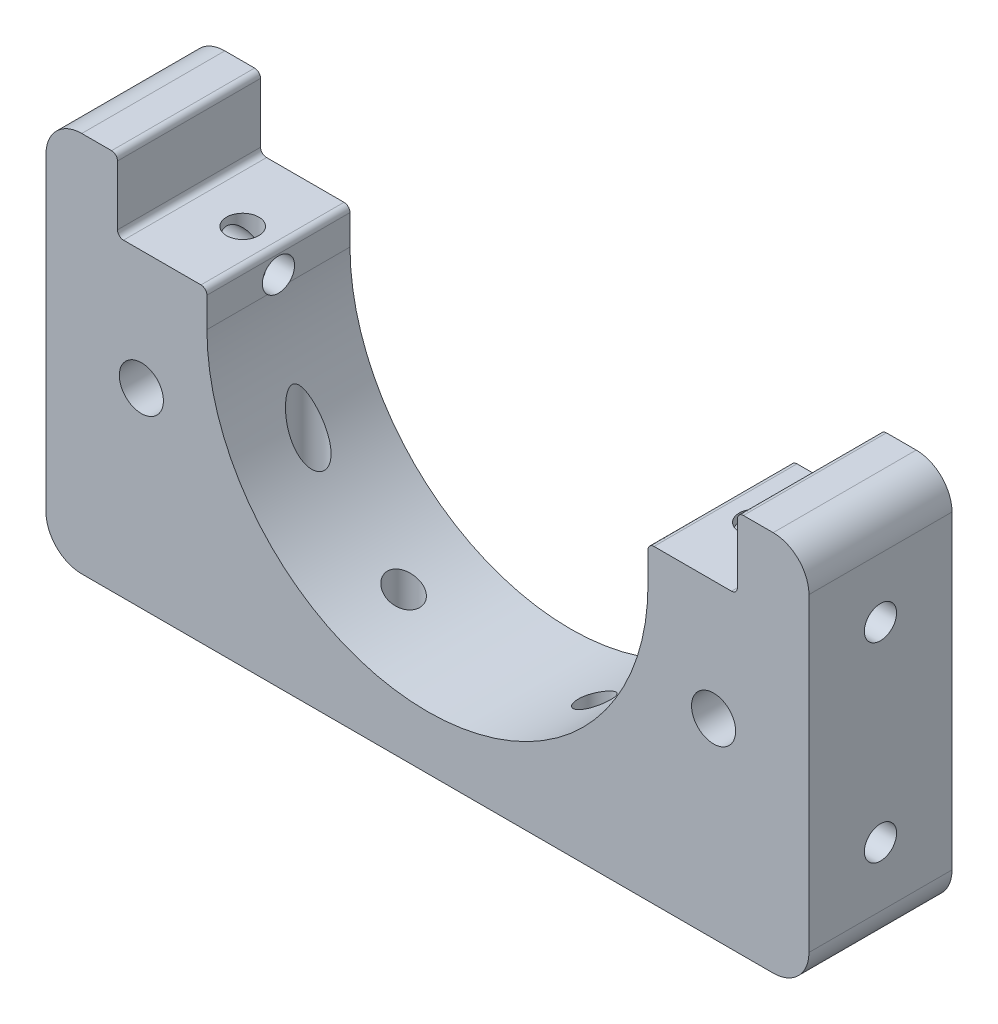
SolidWorks part; units mm, degrees
ref_plane "Front Plane" through (0, 0, 0) normal (0, 0, 1) x (1, 0, 0)
ref_plane "Top Plane" through (0, 0, 0) normal (0, 1, 0) x (1, 0, 0)
ref_plane "Right Plane" through (0, 0, 0) normal (1, 0, 0) x (0, 0, -1)
ref_plane "Plane1" through (0, 0, -6) normal (0, 0, -1) x (-1, 0, 0)
sketch "Sketch1" plane through (0, 0, -6) normal (0, 0, -1) x (-1, 0, 0)
  line L0 (32, -26) -> (32, 6)
  line L1 (32, 6) -> (-32, 6)
  line L2 (-32, 6) -> (-32, -26)
  line L3 (-32, -26) -> (32, -26)
extrude "Boss-Extrude1" add sketch "Sketch1" against normal blind 12
sketch "Sketch2" plane through (0, 0, 6) normal (0, 0, 1) x (1, 0, 0)
  line L0 (-26, 6) -> (-26, 0)
  line L1 (-26, 0) -> (-18.5, 0)
  line L2 (-18.5, 0) -> (-18.5, -3)
  line L3 (18.5, -3) -> (18.5, 6)
  line L4 (18.5, 6) -> (-26, 6)
  arc A0 (-18.5, -3) -> (18.5, -3) centre (0, -3) ccw
extrude "Cut-Extrude1" cut sketch "Sketch2" against normal through all
sketch "Sketch3" plane through (0, 0, 6) normal (0, 0, 1) x (1, 0, 0)
  line L0 (18.5, 0) -> (26, 0)
  line L1 (26, 0) -> (26, 6)
  line L2 (26, 6) -> (18.5, 6)
  line L3 (18.5, 6) -> (18.5, 0)
extrude "Cut-Extrude2" cut sketch "Sketch3" against normal through all
hole_wizard "M2.5 Clearance Hole1" positions "Sketch5" profile "Sketch4" hole size "M2.5" standard "ANSI Metric"
sketch "Sketch5" plane through (0, -26, 0) normal (0, -1, 0) x (-1, 0, 0)
  point P0 (8, 0)
  point P1 (-8, 0)
sketch "Sketch4" plane through (-8, -26, 0) normal (1, 0, 0) x (0, 0, -1)
  line L0 (0, 0) -> (0, 32)
  line L1 (0, 32) -> (1.3525, 32)
  line L2 (1.3525, 32) -> (1.3525, 0)
  line L5 (1.3525, 0) -> (0, 0)
  line L11 (0, -6.35) -> (0, 107.95) construction
  dimension "Thru Hole Dia." = 2.7051
  dimension "Thru Hole Depth" = 32
hole_wizard "M2.5 Clearance Hole2" positions "Sketch7" profile "Sketch6" hole size "M2.5" standard "ANSI Metric"
sketch "Sketch7" plane through (0, -26, 0) normal (0, -1, 0) x (-1, 0, 0)
  point P0 (16, 0)
  point P1 (-16, 0)
sketch "Sketch6" plane through (-16, -26, 0) normal (1, 0, 0) x (0, 0, -1)
  line L0 (0, 0) -> (0, 32)
  line L1 (0, 32) -> (1.3525, 32)
  line L2 (1.3525, 32) -> (1.3525, 0)
  line L5 (1.3525, 0) -> (0, 0)
  line L11 (0, -6.35) -> (0, 107.95) construction
  dimension "Thru Hole Dia." = 2.7051
  dimension "Thru Hole Depth" = 32
hole_wizard "Ø3.7 (3.7) Diameter Hole1" positions "Sketch9" profile "Sketch8" hole size "Ø3.7" standard "ANSI Metric"
sketch "Sketch9" plane through (0, 0, -6) normal (0, 0, -1) x (-1, 0, 0)
  point P0 (24, -10)
sketch "Sketch8" plane through (-24, -10, -6) normal (1, 0, 0) x (0, 1, 0)
  line L0 (0, 0) -> (0, 12)
  line L1 (0, 12) -> (1.85, 12)
  line L2 (1.85, 12) -> (1.85, 0)
  line L5 (1.85, 0) -> (0, 0)
  line L11 (0, -6.35) -> (0, 107.95) construction
  dimension "Thru Hole Dia." = 3.7
  dimension "Thru Hole Depth" = 12
hole_wizard "M2.5 Clearance Hole3" positions "Sketch11" profile "Sketch10" hole size "M2.5" standard "ANSI Metric"
sketch "Sketch11" plane through (0, 0, 0) normal (0, 1, 0) x (1, 0, 0)
  point P0 (21.5, 0)
  point P1 (-21.5, 0)
sketch "Sketch10" plane through (21.5, 0, 0) normal (1, 0, 0) x (0, 0, 1)
  line L0 (0, 0) -> (0, 12.5602)
  line L1 (0, 12.5602) -> (1.3525, 12)
  line L2 (1.3525, 12) -> (1.3525, 0)
  line L5 (1.3525, 0) -> (0, 0)
  line L10 (0, 12.5602) -> (-1.3525, 12) construction
  line L11 (0, -6.35) -> (0, 107.95) construction
  dimension "Hole Dia." = 2.7051
  dimension "Hole Depth" = 12
  dimension "Drill Angle" = 135
hole_wizard "Ø3.7 (3.7) Diameter Hole2" positions "Sketch13" profile "Sketch12" hole size "Ø3.7" standard "ANSI Metric"
sketch "Sketch13" plane through (0, 0, 6) normal (0, 0, 1) x (1, 0, 0)
  point P0 (24, -10)
sketch "Sketch12" plane through (24, -10, 6) normal (1, 0, 0) x (0, -1, 0)
  line L0 (0, 0) -> (0, 12)
  line L1 (0, 12) -> (1.85, 12)
  line L2 (1.85, 12) -> (1.85, 0)
  line L5 (1.85, 0) -> (0, 0)
  line L11 (0, -6.35) -> (0, 107.95) construction
  dimension "Thru Hole Dia." = 3.7
  dimension "Thru Hole Depth" = 12
hole_wizard "M2.5 Clearance Hole4" positions "Sketch15" profile "Sketch14" hole size "M2.5" standard "ANSI Metric"
sketch "Sketch15" plane through (32, 0, 0) normal (1, 0, 0) x (0, 0, -1)
  point P0 (0, -2)
sketch "Sketch14" plane through (32, -2, 0) normal (0, 1, 0) x (0, 0, -1)
  line L0 (0, 0) -> (0, 74.5)
  line L1 (0, 74.5) -> (1.3525, 74.5)
  line L2 (1.3525, 74.5) -> (1.3525, 0)
  line L5 (1.3525, 0) -> (0, 0)
  line L10 (0, 74.5) -> (-1.3526, 74.5) construction
  line L11 (0, -6.35) -> (0, 107.95) construction
  dimension "Hole Dia." = 2.7051
  dimension "Hole Depth" = 74.5
  dimension "Drill Angle" = 180
hole_wizard "M2.5 Clearance Hole5" positions "Sketch17" profile "Sketch16" hole size "M2.5" standard "ANSI Metric"
sketch "Sketch17" plane through (32, 0, 0) normal (1, 0, 0) x (0, 0, -1)
  point P0 (0, -18)
sketch "Sketch16" plane through (32, -18, 0) normal (0, 1, 0) x (0, 0, -1)
  line L0 (0, 0) -> (0, 11.0602)
  line L1 (0, 11.0602) -> (1.3525, 10.5)
  line L2 (1.3525, 10.5) -> (1.3525, 0)
  line L5 (1.3525, 0) -> (0, 0)
  line L10 (0, 11.0602) -> (-1.3525, 10.5) construction
  line L11 (0, -6.35) -> (0, 107.95) construction
  dimension "Hole Dia." = 2.7051
  dimension "Hole Depth" = 10.5
  dimension "Drill Angle" = 135
hole_wizard "M2.5 Clearance Hole6" positions "Sketch19" profile "Sketch18" hole size "M2.5" standard "ANSI Metric"
sketch "Sketch19" plane through (-32, 0, 0) normal (-1, 0, 0) x (0, 0, 1)
  point P0 (0, -18)
sketch "Sketch18" plane through (-32, -18, 0) normal (0, 1, 0) x (0, 0, 1)
  line L0 (0, 0) -> (0, 11.0602)
  line L1 (0, 11.0602) -> (1.3525, 10.5)
  line L2 (1.3525, 10.5) -> (1.3525, 0)
  line L5 (1.3525, 0) -> (0, 0)
  line L10 (0, 11.0602) -> (-1.3525, 10.5) construction
  line L11 (0, -6.35) -> (0, 107.95) construction
  dimension "Hole Dia." = 2.7051
  dimension "Hole Depth" = 10.5
  dimension "Drill Angle" = 135
fillet "Fillet1" radius 0.5 6 edges at (-18.5, 0, 0) (18.5, 0, 0) (26, 6, 0) (-26, 0, 0) (26, 0, 0) (-26, 6, 0) tangent propagation no
fillet "Fillet2" radius 3 4 edges at (-32, 6, 0) (32, 6, 0) (-32, -26, 0) (32, -26, 0) tangent propagation no
